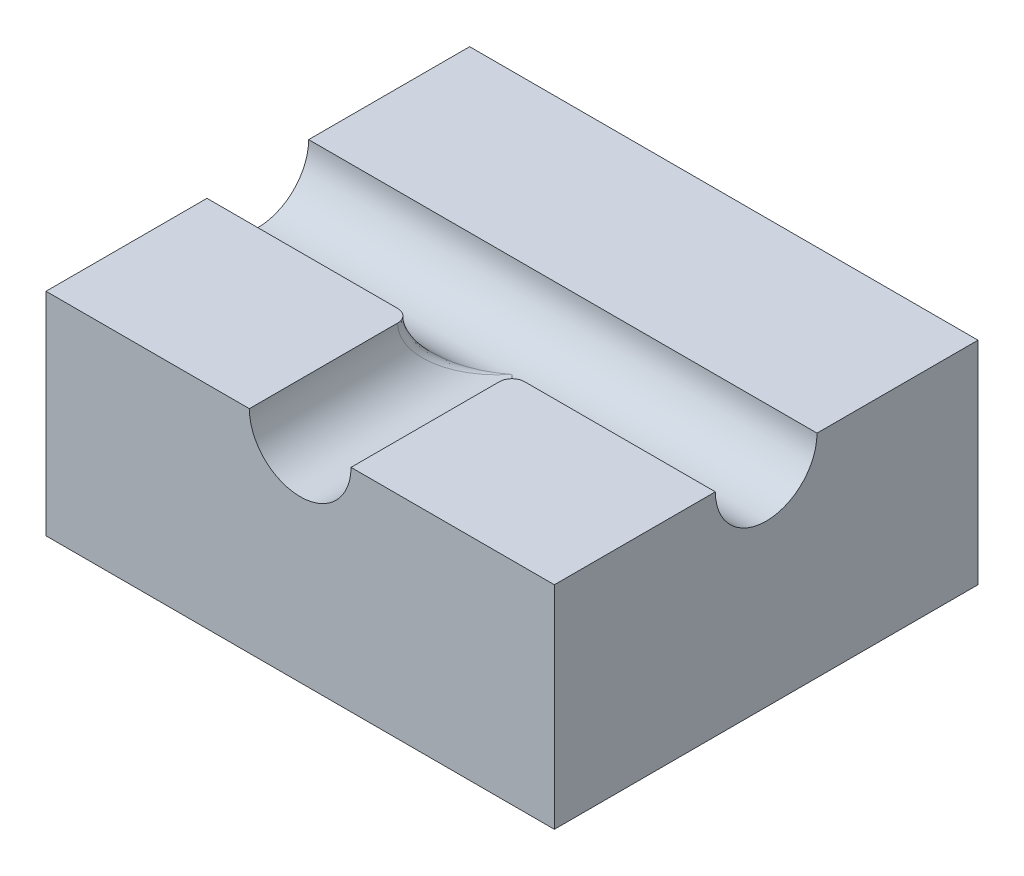
SolidWorks part; units mm, degrees
ref_plane "Front Plane" through (0, 0, 0) normal (0, 0, 1) x (1, 0, 0)
ref_plane "Top Plane" through (0, 0, 0) normal (0, 1, 0) x (1, 0, 0)
ref_plane "Right Plane" through (0, 0, 0) normal (1, 0, 0) x (0, 0, -1)
sketch "Sketch1" plane through (0, 0, 0) normal (0, 0, 1) x (1, 0, 0)
  line L1 (-60, -50) -> (60, -50)
  line L2 (-60, -50) -> (-60, 0)
  line L3 (-60, 0) -> (60, 0)
  line L4 (60, -50) -> (60, 0)
  point P4 (0, 0)
  dimension "D1" = 120
  dimension "D2" = 50
extrude "Boss-Extrude1" add sketch "Sketch1" against normal blind 100
sketch "Sketch2" plane through (0, 0, 0) normal (0, 0, 1) x (1, 0, 0)
  circle A0 centre (0, 0) radius 12
  dimension "D1" = 24
extrude "Cut-Extrude1" cut sketch "Sketch2" against normal blind 50
sketch "Sketch3" plane through (60, 0, 0) normal (1, 0, 0) x (0, 0, -1)
  line L0 (100, 0) -> (0, 0) construction
  circle A0 centre (50, 0) radius 12
  dimension "D1" = 24
extrude "Cut-Extrude2" cut sketch "Sketch3" against normal through all
fillet "Fillet1" radius 3 2 edges at (8.4853, -8.4853, -41.5147) (-8.4853, -8.4853, -41.5147)
